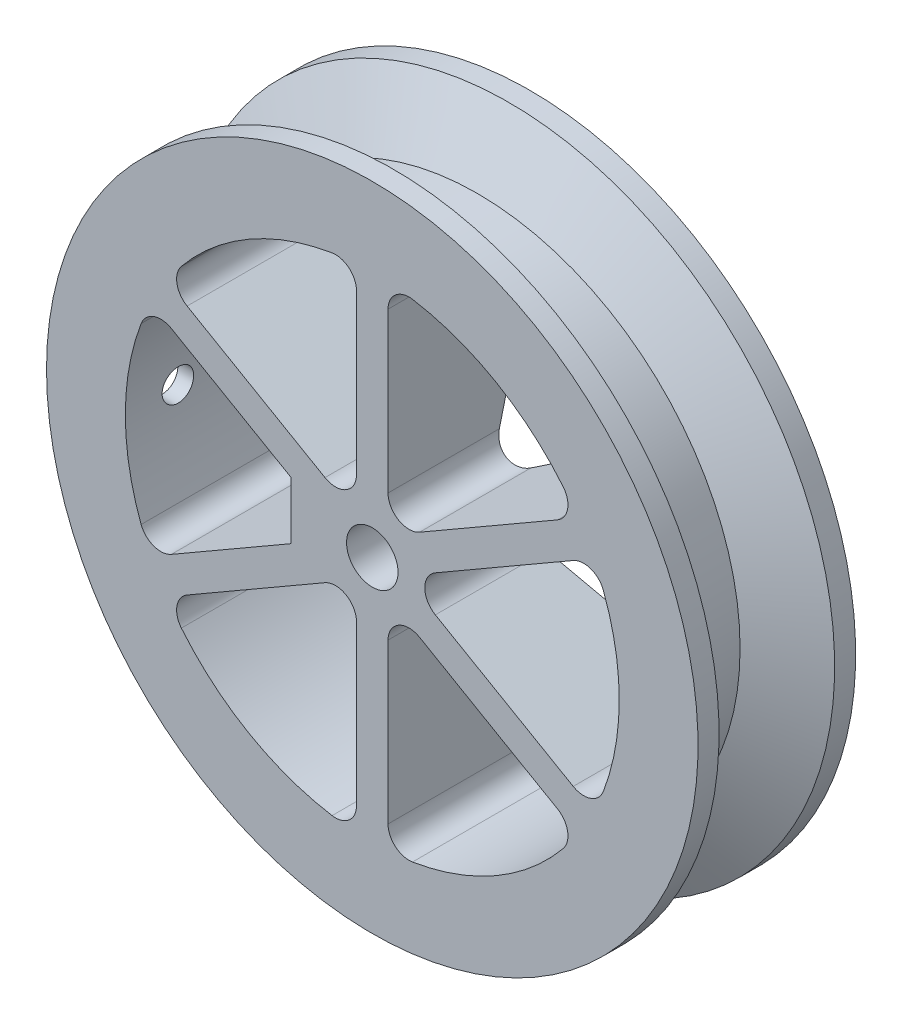
SolidWorks part; units mm, degrees
ref_plane "Front Plane" through (0, 0, 0) normal (0, 0, 1) x (1, 0, 0)
ref_plane "Top Plane" through (0, 0, 0) normal (0, 1, 0) x (1, 0, 0)
ref_plane "Right Plane" through (0, 0, 0) normal (1, 0, 0) x (0, 0, -1)
sketch "Sketch2" plane through (0, 0, 0) normal (0, 1, 0) x (1, 0, 0)
  line L0 (0, 9.525) -> (0, -9.525) construction
  line L1 (0, 9.525) -> (39.37, 9.525)
  line L2 (39.37, 9.525) -> (39.37, 6.985)
  line L3 (39.37, 6.985) -> (31.75, 3.175)
  line L4 (31.75, 3.175) -> (31.75, -6.985)
  line L5 (31.75, -6.985) -> (39.37, -6.985)
  line L6 (39.37, -6.985) -> (39.37, -9.525)
  line L7 (39.37, -9.525) -> (0, -9.525)
  line L8 (0, -9.525) -> (0, 9.525)
  line L9 (0, 0) -> (31.75, 0) construction
  dimension "D1" = 19.05
  dimension "D2" = 2.54
  dimension "D3" = 2.54
  dimension "D4" = 7.62
  dimension "D5" = 31.75
  dimension "D9" = 3.81
revolve "Revolve1" add sketch "Sketch2" angle 360 about L0
sketch "Sketch4" plane through (0, 0, 9.525) normal (0, 0, 1) x (1, 0, 0)
  circle A0 centre (0, 0) radius 3.1115
  dimension "D1" = 6.223
extrude "Cut-Extrude1" cut sketch "Sketch4" against normal through all
sketch "Sketch5" plane through (0, 0, 9.525) normal (0, 0, 1) x (1, 0, 0)
  line L0 (0, 3.175) -> (0, 31.75) construction
  line L1 (2.7496, 1.5875) -> (27.4963, 15.875) construction
  line L2 (5.715, 5.4993) -> (22.3789, 15.1202)
  line L3 (1.905, 7.699) -> (1.905, 26.9408)
  line L4 (3.1259, 4.0044) -> (24.8413, 16.5418) construction
  line L5 (1.905, 4.7093) -> (1.905, 29.7841) construction
  arc A1 (0, 31.75) -> (27.4963, 15.875) centre (0, 0) cw construction
  arc A2 (2.7496, 1.5875) -> (0, 3.175) centre (0, 0) ccw construction
  arc A3 (4.8585, 29.4469) -> (23.0725, 18.931) centre (0, 0) cw
  arc A4 (3.1259, 4.0044) -> (1.905, 4.7093) centre (0, 0) ccw
  arc A5 (5.715, 5.4993) -> (1.905, 7.699) centre (4.445, 7.699) cw
  arc A6 (1.905, 29.7841) -> (24.8413, 16.5418) centre (0, 0) cw construction
  arc A7 (4.8585, 29.4469) -> (1.905, 26.9408) centre (4.445, 26.9408) ccw
  arc A8 (23.0725, 18.931) -> (22.3789, 15.1202) centre (21.1089, 17.3199) cw
  dimension "D1" = 31.75
  dimension "D3" = 6.35
  dimension "D5" = 2.54
  dimension "D2" = 60
  dimension "D4" = 1.905
extrude "Cut-Extrude2" cut sketch "Sketch5" against normal through all contours A8 A3 A7 L3 A5 L2 | A5 L2 L3 region at (10.2965, 17.834, 9.525)
pattern_circular "CirPattern1" count 6 over 360 about axis through (0, 0, 9.525) along (0, 0, -1) of "Cut-Extrude2"
sketch "Sketch6" plane through (0, 0, 9.525) normal (0, 0, 1) x (1, 0, 0)
  line L0 (-3.1115, 0) -> (-6.35, 0) construction
  line L2 (-4.7307, -3.4645) -> (-9.8107, -3.4645)
  line L3 (-4.7307, -3.4645) -> (-4.7307, 3.4645)
  line L4 (-4.7307, 3.4645) -> (-9.8107, 3.4645)
  line L5 (-9.8107, -3.4645) -> (-9.8107, 3.4645)
  line L6 (-7.62, 2.1997) -> (-24.2839, 11.8206) construction
  circle A0 centre (0, 0) radius 3.1115 construction
  arc A1 (-7.62, -2.1997) -> (-7.62, 2.1997) centre (-8.89, 0) ccw construction
  point P11 (-4.7307, 0)
  dimension "D1" = 5.08
extrude "Boss-Extrude2" add sketch "Sketch6" against normal through all
hole_wizard "#4 Clearance Hole1" positions "Sketch8" profile "Sketch9" hole size "#4" standard "ANSI Inch"
sketch "Sketch8" plane through (-9.8107, 0, 0) normal (-1, 0, 0) x (0, 0, 1)
  line L0 (-3.175, 0) -> (6.985, 0) construction
  line L1 (-3.175, 31.75) -> (-3.175, -31.75) construction
  line L2 (6.985, 31.75) -> (6.985, -31.75) construction
  point P0 (3.175, 0)
  dimension "D1" = 3.81
sketch "Sketch9" plane through (-9.8107, 0, 3.175) normal (0, 1, 0) x (0, 0, 1)
  line L0 (0, 0) -> (0, 13.7378)
  line L1 (0, 13.7378) -> (1.7272, 12.7)
  line L2 (1.7272, 12.7) -> (1.7272, 0)
  line L5 (1.7272, 0) -> (0, 0)
  line L10 (0, 13.7378) -> (-1.7272, 12.7) construction
  line L11 (0, -6.35) -> (0, 107.95) construction
  dimension "Hole Dia." = 3.4544
  dimension "Hole Depth" = 12.7
  dimension "Drill Angle" = 118
sketch "Sketch10" plane through (-9.8107, 0, 0) normal (-1, 0, 0) x (0, 0, 1)
  circle A0 centre (3.175, 0) radius 1.905
  dimension "D1" = 3.81
extrude "Cut-Extrude3" cut sketch "Sketch10" along normal through all
sketch "Sketch15" plane through (-9.8107, 0, 0) normal (-1, 0, 0) x (0, 0, 1)
  line L0 (3.175, 0) -> (-9.525, 0) construction
  line L1 (-9.525, 39.37) -> (-9.525, -39.37) construction
  line L2 (-9.525, -3.429) -> (5.1547, -3.429)
  line L3 (-0.4912, 0) -> (1.3419, -3.175) construction
  line L4 (1.3419, -3.175) -> (5.0081, -3.175) construction
  line L5 (5.0081, -3.175) -> (6.8412, 0) construction
  line L6 (6.8412, 0) -> (5.0081, 3.175) construction
  line L7 (5.0081, 3.175) -> (1.3419, 3.175) construction
  line L8 (1.3419, 3.175) -> (-0.4912, 0) construction
  line L9 (5.1547, -3.429) -> (7.1345, 0)
  line L10 (7.1345, 0) -> (5.1547, 3.429)
  line L11 (5.1547, 3.429) -> (-9.525, 3.429)
  line L12 (5.1547, 3.429) -> (1.3419, 3.429) construction
  line L13 (1.3419, -3.429) -> (5.1547, -3.429) construction
  line L14 (-9.525, 3.429) -> (-9.525, -3.429)
  circle A0 centre (3.175, 0) radius 3.175 construction
  dimension "D1" = 6.35
  dimension "D2" = 0.254
extrude "Cut-Extrude7" cut sketch "Sketch15" against normal blind 2.413 from offset 1.778 offset against normal yes
sketch "Sketch13" plane through (0, 0, 0) normal (1, 0, 0) x (0, 0, -1)
  circle A0 centre (0, 0) radius 1
  dimension "D1" = 2
extrude "Cut-Extrude6" [suppressed] cut sketch "Sketch13" along normal through all from offset 25.4
sketch "Sketch16" plane through (0, 0, 0) normal (0, 1, 0) x (1, 0, 0)
  line L0 (0, -9.525) -> (0, 9.525) construction
  line L1 (3.1115, 9.525) -> (-3.1115, 9.525) construction
  line L2 (-39.37, -9.525) -> (39.37, -9.525) construction
  line L3 (0, 1.905) -> (29.845, 9.525)
  line L4 (29.845, 9.525) -> (0, 9.525)
  line L5 (0, 9.525) -> (0, 1.905)
  dimension "D1" = 7.62
revolve "Cut-Revolve1" cut sketch "Sketch16" angle 360 about L0
sketch "Sketch14" plane through (0, 0, 9.525) normal (0, 0, -1) x (-1, 0, 0)
  line L0 (0, 0) -> (39.37, 0) construction
  circle A0 centre (39.37, 0) radius 5.08
  circle A1 centre (0, 0) radius 39.37 construction
  circle A2 centre (0, -39.37) radius 5.08
  circle A3 centre (-39.37, 0) radius 5.08
  circle A4 centre (0, 39.37) radius 5.08
  point P15 (0, 0)
  dimension "D1" = 10.16
  dimension "D2" = 4
extrude "Print Tabs" [suppressed] add sketch "Sketch14" along normal blind 0.4
equation "\"spool_radius\"=1.25"
